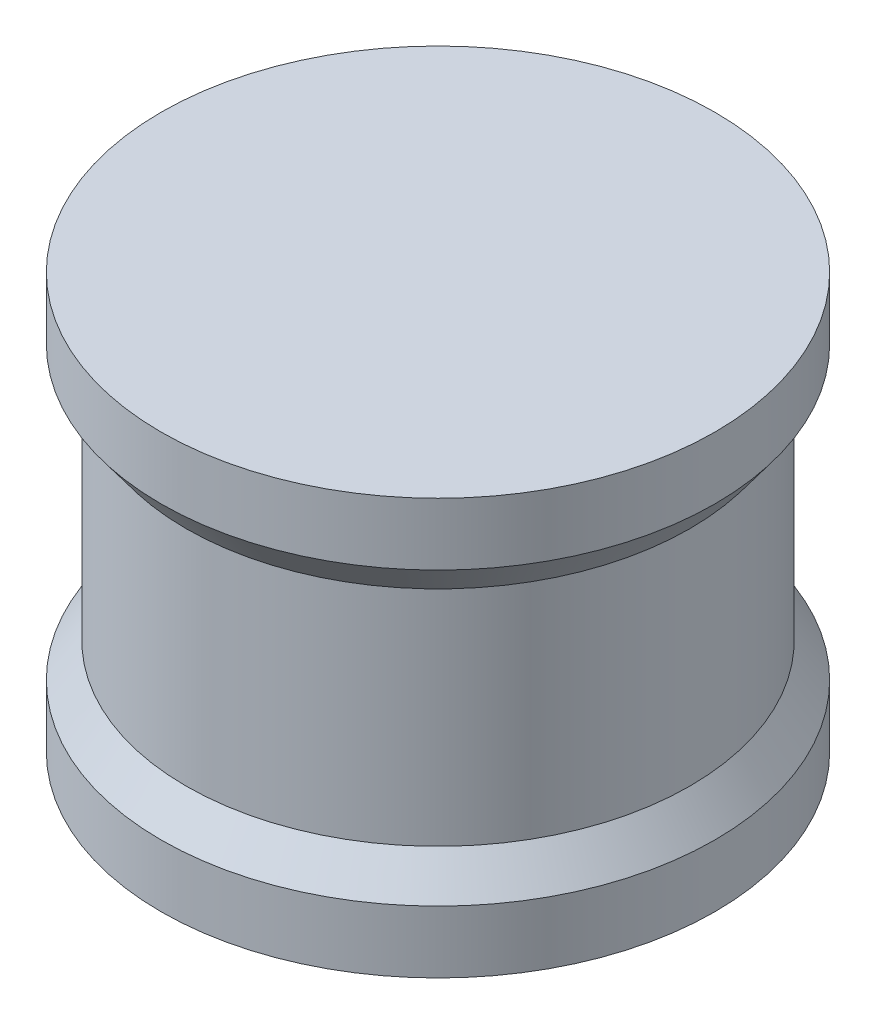
SolidWorks part; units mm, degrees
material "ABS"
ref_plane "Front Plane" through (0, 0, 0) normal (0, 0, 1) x (1, 0, 0)
ref_plane "Top Plane" through (0, 0, 0) normal (0, 1, 0) x (1, 0, 0)
ref_plane "Right Plane" through (0, 0, 0) normal (1, 0, 0) x (0, 0, -1)
sketch "Sketch2" plane through (0, 0, 0) normal (0, 1, 0) x (1, 0, 0)
  circle A0 centre (0, 0) radius 20
  dimension "D1" = 40
extrude "Boss-Extrude1" add sketch "Sketch2" along normal blind 30
sketch "Sketch3" plane through (0, 0, 0) normal (0, 0, 1) x (1, 0, 0)
  line L0 (-20, 30) -> (-20, 25.5071) construction
  line L1 (-20, 30) -> (-20, 0) construction
  line L2 (-20, 25.5071) -> (-18.1877, 23.0494)
  line L3 (-18.1877, 23.0494) -> (-18.1877, 6.9506)
  line L4 (-20, 0) -> (-20, 4.4929) construction
  line L6 (20, 15) -> (-20, 15) construction
  line L7 (20, 0) -> (20, 30) construction
  line L8 (-20, 4.4929) -> (-18.1877, 6.9506)
  line L9 (-20, 25.5071) -> (-20, 4.4929)
  point P17 (-18.1877, 15)
revolve "Cut-Revolve1" cut sketch "Sketch3" angle 360 about axis through (0, 30, 0) along (0, -1, 0)
sketch "Sketch5" plane through (0, 0, 0) normal (0, 0, 1) x (1, 0, 0)
  point P0 (20, 0)
ref_axis "Axis1" through (20, 0, 0) along (0, 0, 1)
